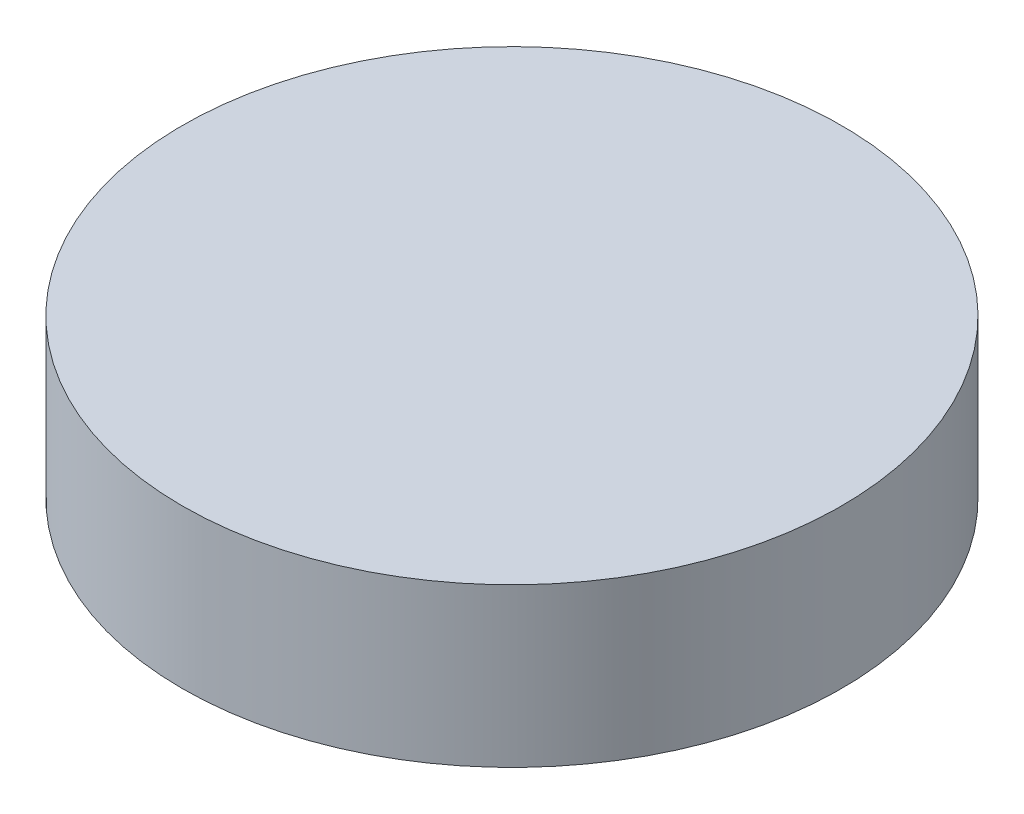
SolidWorks part; units mm, degrees
ref_plane "Front Plane" through (0, 0, 0) normal (0, 0, 1) x (1, 0, 0)
ref_plane "Top Plane" through (0, 0, 0) normal (0, 1, 0) x (1, 0, 0)
ref_plane "Right Plane" through (0, 0, 0) normal (1, 0, 0) x (0, 0, -1)
sketch "Sketch1" plane through (0, 0, 0) normal (0, 1, 0) x (1, 0, 0)
  circle A0 centre (0, 0) radius 6.25
  dimension "D1" = 12.5
extrude "Boss-Extrude1" add sketch "Sketch1" along normal blind 3
